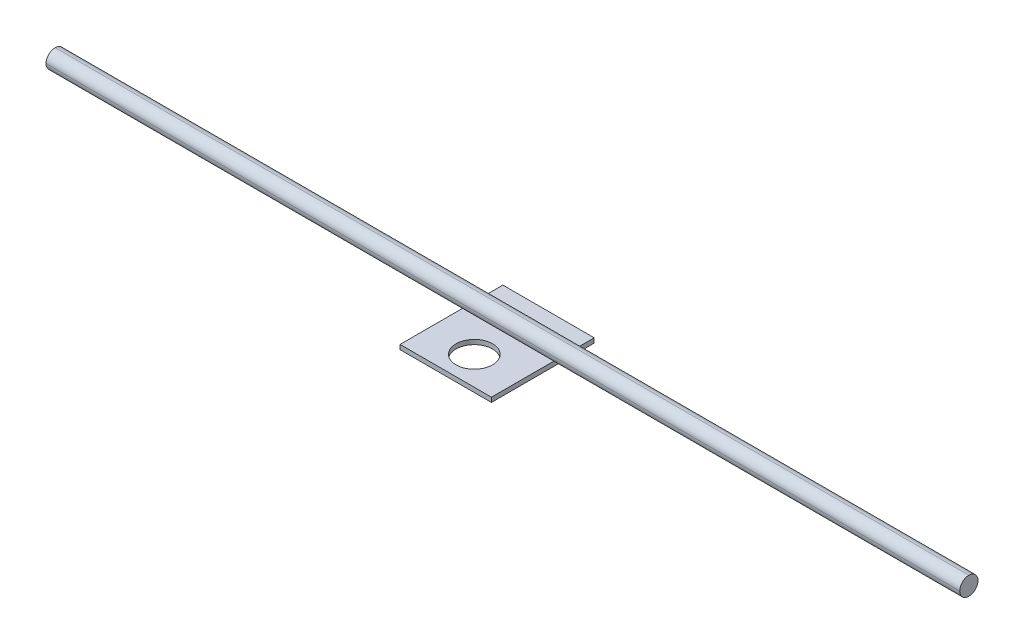
SolidWorks part; units mm, degrees
ref_plane "Front Plane" through (0, 0, 0) normal (0, 0, 1) x (1, 0, 0)
ref_plane "Top Plane" through (0, 0, 0) normal (0, 1, 0) x (1, 0, 0)
ref_plane "Right Plane" through (0, 0, 0) normal (1, 0, 0) x (0, 0, -1)
sketch "Sketch3" plane through (0, 0, 0) normal (0, 1, 0) x (1, 0, 0)
  line L1 (-20, -22.5) -> (20, -22.5)
  line L2 (-20, -22.5) -> (-20, 22.5)
  line L3 (-20, 22.5) -> (20, 22.5)
  line L4 (20, -22.5) -> (20, 22.5)
  line L5 (-20, -22.5) -> (20, 22.5) construction
  line L6 (-20, 22.5) -> (20, -22.5) construction
  point P0 (0, 0)
extrude "Boss-Extrude1" add sketch "Sketch3" along normal blind 2
sketch "Sketch4" plane through (0, 2, 0) normal (0, 1, 0) x (1, 0, 0)
  line L0 (0, -22.5) -> (0, 2.5)
  line L1 (-20, -22.5) -> (20, -22.5) construction
  line L3 (-200, 2.5) -> (200, 2.5)
  line L4 (-200, 2.5) -> (-200, 10.5)
  line L5 (-200, 10.5) -> (200, 10.5)
  line L6 (200, 2.5) -> (200, 10.5)
  point P9 (0, 2.5)
  dimension "D1" = 8
  dimension "D2" = 400
extrude "Boss-Extrude3" add sketch "Sketch4" along normal blind 8 separate body contours L5 L4 L3 | L3 L6 L5 L0 | L5 L3 L0 region at (0, 2, -6.5)
fillet "Fillet2" radius 4 4 edges at (0, 2, -10.5) (0, 2, -2.5) (0, 10, -2.5) (0, 10, -10.5)
sketch "Sketch5" plane through (0, 2, 0) normal (0, 1, 0) x (1, 0, 0)
  circle A0 centre (0, -10) radius 8
extrude "Cut-Extrude1" cut sketch "Sketch5" against normal through all
